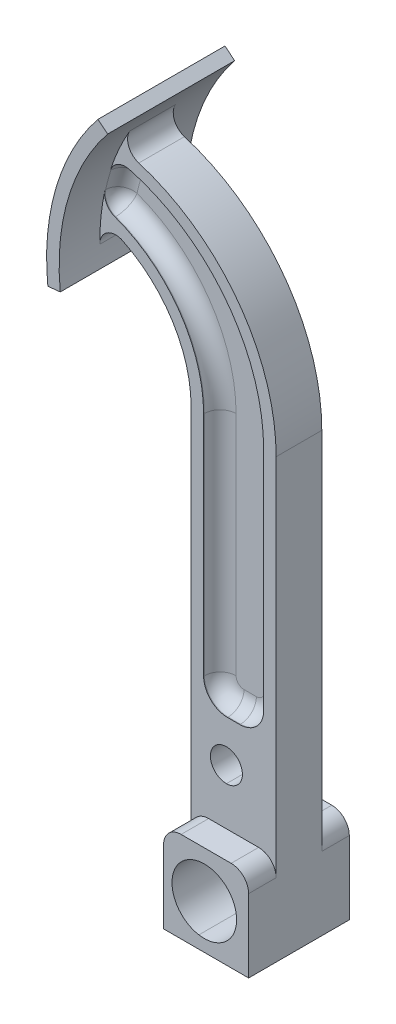
SolidWorks part; units mm, degrees
material "6061-T6 (SS)"
ref_plane "Front Plane" through (0, 0, 0) normal (0, 0, 1) x (1, 0, 0)
ref_plane "Top Plane" through (0, 0, 0) normal (0, 1, 0) x (1, 0, 0)
ref_plane "Right Plane" through (0, 0, 0) normal (1, 0, 0) x (0, 0, -1)
sketch "Sketch2" plane through (0, 0, 0) normal (0, 0, 1) x (1, 0, 0)
  line L0 (-14.11, 39.4147) -> (-14.11, -58.25)
  line L1 (-14.11, -58.25) -> (19.89, -58.25)
  line L2 (19.89, -58.25) -> (19.89, 39.4147)
  line L3 (0, 6.4) -> (0, 146.4) construction
  line L4 (0, 146.4) -> (0, 214.25) construction
  line L5 (-55.11, 146.4) -> (-50.1368, 146.9172)
  line L6 (-35.11, 214.2) -> (-31.2138, 211.0664)
  line L7 (19.89, 39.4147) -> (19.89, 116.75)
  line L8 (-14.11, 39.4147) -> (-14.11, 117.0542)
  circle A0 centre (0, 0) radius 6.4
  circle A1 centre (2.16, -40.52) radius 12.92
  arc A2 (-55.11, 146.4) -> (-35.11, 214.2) centre (37.2478, 156.0057) cw
  arc A3 (-50.1368, 146.9172) -> (-31.2138, 211.0664) centre (37.2478, 156.0057) cw
  arc A4 (19.89, 116.75) -> (-42.4952, 192.8802) centre (-57.7544, 116.75) ccw
  arc A5 (-14.11, 117.0542) -> (-50.2325, 164.1217) centre (-62.8357, 117.0542) ccw
  point P13 (-55.11, 146.4)
  point P15 (-35.11, 214.2)
  dimension "D1" = 12.8
  dimension "D2" = 14.11
  dimension "D3" = 25.84
  dimension "D4" = 16.27
  dimension "D5" = 40.52
  dimension "D6" = 34
  dimension "D7" = 17.73
  dimension "D8" = 140
  dimension "D9" = 272.5
  dimension "D10" = 41
  dimension "D11" = 20
  dimension "D13" = 175
  dimension "D14" = 67.8
  dimension "D12" = 5
extrude "Boss-Extrude1" add sketch "Sketch2" along normal mid plane 40.25 contours A5 L8 L0 L1 L2 L7 A4 A3 A1 A0 region at (-2.5856, 77.1621, 0)
extrude "Boss-Extrude2" add sketch "Sketch2<3>" along normal mid plane 50.8 contours L5 A3 L6 A2 region at (-47.2521, 180.9319, 0)
sketch "Sketch2<3>" plane through (0, 0, 0) normal (0, 0, 1) x (1, 0, 0) same geometry as "Sketch2"
sketch "Sketch3" plane through (0, 0, 20.125) normal (0, 0, 1) x (1, 0, 0)
  line L0 (-14.11, -58.25) -> (-14.11, 117.0542) construction
  line L1 (19.89, -58.25) -> (19.89, 116.75) construction
  line L2 (-14.11, -58.25) -> (-14.11, 117.0542) construction
  line L3 (19.89, -58.25) -> (19.89, 116.75) construction
  line L4 (-9.11, 16.7433) -> (-9.11, 117.0542)
  line L5 (14.89, 16.7433) -> (14.89, 116.75)
  line L6 (14.89, 16.7433) -> (-9.11, 16.7433)
  line L7 (-9.11, -58.25) -> (-9.11, 117.0542) construction
  line L8 (14.89, -58.25) -> (14.89, 116.75) construction
  arc A0 (-14.11, 117.0542) -> (-50.2325, 164.1217) centre (-62.8357, 117.0542) ccw construction
  arc A1 (19.89, 116.75) -> (-42.4952, 192.8802) centre (-57.7544, 116.75) ccw construction
  arc A2 (-14.11, 117.0542) -> (-50.2325, 164.1217) centre (-62.8357, 117.0542) ccw construction
  arc A3 (19.89, 116.75) -> (-42.4952, 192.8802) centre (-57.7544, 116.75) ccw construction
  arc A4 (-9.11, 117.0542) -> (-49.6224, 169.1297) centre (-62.8357, 117.0542) ccw
  arc A5 (14.89, 116.75) -> (-44.5063, 188.1762) centre (-57.7544, 116.75) ccw
  arc A6 (-42.4952, 192.8802) -> (-50.2325, 164.1217) centre (37.2478, 156.0057) ccw construction
  arc A7 (-44.5063, 188.1762) -> (-49.6224, 169.1297) centre (37.2478, 156.0057) ccw
  arc A8 (-9.11, 117.0542) -> (-48.9392, 168.9516) centre (-62.8357, 117.0542) ccw construction
  arc A9 (14.89, 116.75) -> (-43.4778, 187.9777) centre (-57.7544, 116.75) ccw construction
  dimension "D1" = 5
  dimension "D2" = 5
extrude "Cut-Extrude1" cut sketch "Sketch3" against normal blind 17.625
fillet "Fillet2" radius 9.525 2 edges at (14.89, 16.7433, 11.3125) (-9.11, 16.7433, 11.3125)
fillet "Fillet1" radius 6.35 10 edges at (-9.11, 71.6612, 2.5) (2.89, 16.7433, 2.5) (14.89, 71.5091, 2.5) (-1.8992, 163.1979, 2.5) (-20.4308, 150.0433, 2.5) (-44.5063, 188.1762, 11.3125) (-49.6224, 169.1297, 11.3125) (-47.6005, 178.7969, 2.5) (12.1002, 19.5331, 2.5) (-6.3202, 19.5331, 2.5)
mirror "Mirror1" about plane through (0, 0, 0) normal (0, 0, 1) of "Fillet2", "Fillet1", "Cut-Extrude1"
sketch "Sketch4" plane through (0, 0, 0) normal (0, 0, 1) x (1, 0, 0)
  line L0 (0, -67.2871) -> (0, 29.4577)
split line "Split Line1"
sketch "Sketch5" plane through (19.89, 0, 0) normal (1, 0, 0) x (0, 0, -1)
  line L0 (-20.125, 29.25) -> (-12, 192.8802)
  line L1 (-20.125, -58.25) -> (-20.125, 116.75) construction
  line L2 (-20.125, 192.8802) -> (20.125, 192.8802) construction
  line L3 (-12, 192.8802) -> (-20.125, 192.8802)
  line L4 (-20.125, 192.8802) -> (-20.125, 29.25)
  line L5 (0, 41.524) -> (0, -41.524) construction
  dimension "D1" = 12
extrude "Cut-Extrude3" cut sketch "Sketch5" against normal up to surface (62.3852 mm away) up to face at (-47.1971, 178.7052, 0)
extrude "Cut-Extrude4" cut sketch "Sketch5<2>" against normal up to surface (34 mm away) up to face at (-14.11, 47.8428, 5.5226)
sketch "Sketch5<2>" plane through (19.89, 0, 0) normal (1, 0, 0) x (0, 0, -1) same geometry as "Sketch5"
mirror "Mirror3" about plane through (0, 0, 0) normal (0, 0, 1) of "Cut-Extrude3", "Cut-Extrude4"
fillet "Fillet3" radius 6.35 2 edges at (-42.4952, 192.8802, 0) (-50.2325, 164.1217, 0)
sketch "Sketch6" plane through (0, 0, 0) normal (0, 0, 1) x (1, 0, 0)
  circle A0 centre (2.8868, 42.5413) radius 7.5129
  circle A1 centre (2.8868, 65.3736) radius 7.5129
  circle A2 centre (2.8868, 86.1836) radius 7.5129
  circle A3 centre (2.8868, 107) radius 7.5129
  circle A4 centre (1.0143, 133.245) radius 7.5129
  circle A5 centre (-9.5959, 155.6117) radius 7.5129
  circle A6 centre (-25.8681, 170.935) radius 7.5129
extrude "Cut-Extrude5" [suppressed] cut sketch "Sketch6" against normal through all both and the other way through all
sketch "Sketch7" plane through (0, 0, 20.125) normal (0, 0, 1) x (1, 0, 0)
  line L0 (-22.4767, -22.0349) -> (33.3209, -22.0349)
  line L1 (33.3209, -22.0349) -> (33.3209, 196.8789)
  line L2 (33.3209, 196.8789) -> (-31.2138, 211.0664)
  line L3 (-50.1368, 146.9172) -> (-22.4767, -22.0349)
  arc A1 (-31.2138, 211.0664) -> (-50.1368, 146.9172) centre (37.2478, 156.0057) ccw
extrude "Cut-Extrude6" cut sketch "Sketch7" against normal blind 11
mirror "Mirror4" about plane through (0, 0, 0) normal (0, 0, 1) of "Cut-Extrude6"
fillet "Fillet4" radius 7 4 edges at (-14.11, -22.0349, -14.625) (19.89, -22.0349, -14.625) (19.89, -22.0349, 14.625) (-14.11, -22.0349, 14.625)
